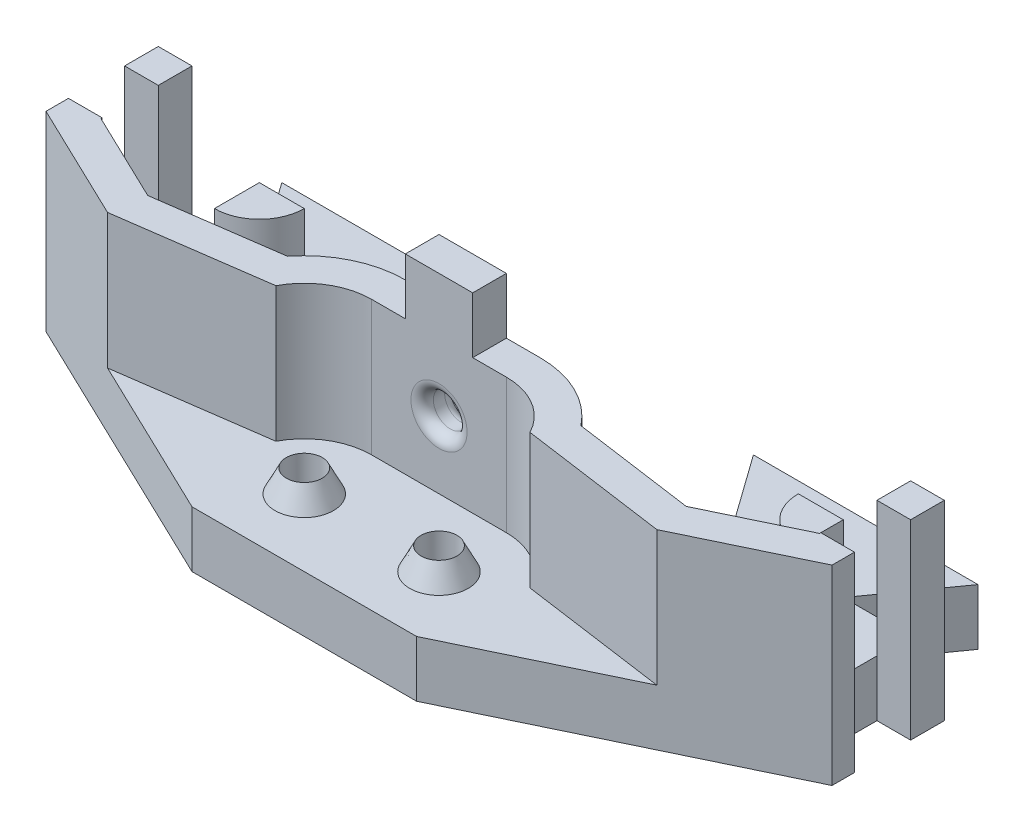
SolidWorks part; units mm, degrees
ref_plane "Front Plane" through (0, 0, 0) normal (0, 0, 1) x (1, 0, 0)
ref_plane "Top Plane" through (0, 0, 0) normal (0, 1, 0) x (1, 0, 0)
ref_plane "Right Plane" through (0, 0, 0) normal (1, 0, 0) x (0, 0, -1)
sketch "Sketch1" plane through (0, 0, 0) normal (0, 1, 0) x (1, 0, 0)
  line L0 (0, 0) -> (20, 0)
  line L1 (10, 0) -> (10, 12) construction
  line L2 (10, 12) -> (-25, 12) construction
  line L3 (0, 0) -> (-25, 12)
  line L4 (-25, 12) -> (-25, 22)
  line L5 (-25, 22) -> (45, 22)
  line L6 (45, 22) -> (45, 12)
  line L7 (45, 12) -> (20, 0)
  dimension "D1" = 35
  dimension "D2" = 20
  dimension "D3" = 12
  dimension "D4" = 70
  dimension "D5" = 10
  dimension "D6" = 10
extrude "Boss-Extrude1" add sketch "Sketch1" along normal blind 5
sketch "Sketch2" plane through (0, 5, 0) normal (0, 1, 0) x (1, 0, 0)
  line L0 (10, 0) -> (10, 22) construction
  line L1 (0, 0) -> (20, 0) construction
  line L2 (45, 22) -> (-25, 22) construction
  circle A0 centre (4, 6) radius 1.6
  circle A1 centre (16, 6) radius 1.6
  dimension "D1" = 3.2
  dimension "D2" = 6
  dimension "D3" = 6
extrude "Cut-Extrude1" cut sketch "Sketch2" against normal blind 3
sketch "Sketch3" plane through (0, 5, 0) normal (0, 1, 0) x (1, 0, 0)
  line L0 (4, 6) -> (-8.7631, 4.2063) construction
  line L1 (-25, 12) -> (0, 0) construction
  line L2 (-8.7631, 4.2063) -> (-8.7631, 22) construction
  line L3 (45, 22) -> (-25, 22) construction
  line L4 (-2.3815, 5.1031) -> (-2.8686, 8.5691) construction
  line L5 (-2.8686, 8.5691) -> (4.0027, 9.5348) construction
  line L6 (-1.3131, 8.7877) -> (-14.4587, 6.9402)
  line L7 (10, 0) -> (10, 22) construction
  line L8 (0, 0) -> (20, 0) construction
  line L10 (-14.4587, 6.9402) -> (-25, 12)
  line L11 (-25, 12) -> (-25, 22)
  line L12 (-25, 22) -> (-22, 22)
  line L13 (-21.9703, 13.8734) -> (-25, 15.3277) construction
  line L14 (-21.9703, 13.8734) -> (-9.0961, 7.6939) construction
  line L15 (-19.7294, 9.4701) -> (-13.715, 22) construction
  line L17 (-3.069, 11.5704) -> (-13.9782, 10.0372)
  line L19 (-7.8859, 7.8639) -> (-9.8726, 22) construction
  line L21 (4, 12) -> (4, 15) construction
  line L30 (-22, 22) -> (-22, 13.8877)
  line L32 (0.4296, 9.0326) -> (0.012, 12.0034) construction
  line L33 (0.012, 12.0034) -> (-19.3407, 9.2836) construction
  line L34 (-22, 13.8877) -> (-13.9782, 10.0372)
  line L35 (4, 15) -> (16, 15)
  line L36 (4, 12) -> (16, 12)
  line L37 (21.3131, 8.7877) -> (34.4587, 6.9402)
  line L38 (34.4587, 6.9402) -> (45, 12)
  line L39 (45, 12) -> (45, 22)
  line L40 (45, 22) -> (42, 22)
  line L41 (42, 22) -> (42, 13.8877)
  line L42 (42, 13.8877) -> (33.9782, 10.0372)
  line L43 (23.069, 11.5704) -> (33.9782, 10.0372)
  arc A0 (-1.3131, 8.7877) -> (4, 12) centre (4, 6) cw
  arc A4 (4, 15) -> (-3.069, 11.5704) centre (4, 6) ccw
  arc A5 (21.3131, 8.7877) -> (16, 12) centre (16, 6) ccw
  arc A6 (16, 15) -> (23.069, 11.5704) centre (16, 6) cw
  point P34 (10, 12)
  point P35 (10, 12)
  point P36 (10, 15)
  point P52 (10, 15)
  dimension "D4" = 6
  dimension "D1" = 82
  dimension "D2" = 3.5
  dimension "D3" = 90
  dimension "D5" = 90
  dimension "D6" = 90
  dimension "D7" = 3
  dimension "D8" = 3
  dimension "D9" = 3
  dimension "D10" = 3
  dimension "D11" = 3
  dimension "D12" = 90
extrude "Boss-Extrude2" add sketch "Sketch3" along normal blind 12
ref_plane "Plane1" through (0, 0, -6) normal (0, 0, 1) x (1, 0, 0)
sketch "Sketch6" plane through (0, 0, -6) normal (0, 0, 1) x (1, 0, 0)
  line L0 (2.4, 5) -> (2.4, 7)
  line L1 (2.4, 7) -> (1.4, 5)
  line L2 (1.4, 5) -> (2.4, 5)
  line L3 (2.4, 5) -> (5.6, 5) construction
  line L4 (4, 5) -> (4, 7.7373) construction
  dimension "D1" = 2
  dimension "D2" = 1
revolve "Revolve1" add sketch "Sketch6" angle 360 about L4
sketch "Sketch7" plane through (0, 0, -6) normal (0, 0, 1) x (1, 0, 0)
  line L0 (14.4, 5) -> (14.4, 7)
  line L1 (14.4, 7) -> (13.4, 5)
  line L2 (13.4, 5) -> (14.4, 5)
  line L3 (14.4, 5) -> (17.6, 5) construction
  line L4 (16, 5) -> (16, 8.947) construction
  dimension "D1" = 2
  dimension "D2" = 1
revolve "Revolve2" add sketch "Sketch7" angle 360 about L4
sketch "Sketch8" plane through (0, 0, -12) normal (0, 0, 1) x (1, 0, 0)
  line L0 (10, 17) -> (10, 5) construction
  line L1 (4, 17) -> (16, 17) construction
  line L2 (4, 5) -> (16, 5) construction
  circle A0 centre (10, 11) radius 1.5
  dimension "D1" = 3
extrude "Cut-Extrude2" cut sketch "Sketch8" against normal blind 3
fillet "Fillet1" radius 1 2 edges at (11.5, 11, -15) (11.5, 11, -12)
sketch "Sketch9" plane through (0, 17, 0) normal (0, 1, 0) x (1, 0, 0)
  line L0 (10, 12) -> (10, 15) construction
  line L1 (4, 12) -> (16, 12) construction
  line L2 (16, 15) -> (4, 15) construction
  line L3 (16, 15) -> (4, 15) construction
  line L4 (7, 12) -> (13, 12)
  line L5 (7, 12) -> (7, 15)
  line L6 (7, 15) -> (13, 15)
  line L7 (13, 12) -> (13, 15)
  dimension "D1" = 3
  dimension "D2" = 3
extrude "Boss-Extrude3" add sketch "Sketch9" along normal blind 5
sketch "Sketch12" plane through (0, 17, 0) normal (0, 1, 0) x (1, 0, 0)
  line L0 (-25, 22) -> (-25, 12) construction
  line L1 (-25, 19) -> (-22, 19)
  line L2 (-25, 19) -> (-25, 14)
  line L3 (-25, 14) -> (-22, 14)
  line L4 (-22, 19) -> (-22, 14)
  line L5 (-22, 13.8877) -> (-22, 22) construction
  line L6 (-22, 22) -> (-25, 22) construction
  line L7 (10, 22) -> (10, 0) construction
  line L8 (42, 22) -> (-22, 22) construction
  line L9 (0, 0) -> (20, 0) construction
  line L10 (45, 14) -> (42, 14)
  line L11 (42, 19) -> (42, 14)
  line L12 (45, 19) -> (42, 19)
  line L13 (45, 19) -> (45, 14)
  dimension "D1" = 3
  dimension "D2" = 5
extrude "Cut-Extrude4" cut sketch "Sketch12" against normal blind 17
sketch "Sketch14" plane through (0, 5, 0) normal (0, 1, 0) x (1, 0, 0)
  line L0 (42, 22) -> (-22, 22) construction
  line L1 (32, 22) -> (36, 22)
  line L2 (32, 22) -> (32, 18)
  line L3 (32, 18) -> (36, 18)
  line L4 (36, 22) -> (36, 18)
  line L5 (10, 22) -> (10, 0) construction
  line L6 (0, 0) -> (20, 0) construction
  line L7 (-12, 18) -> (-16, 18)
  line L8 (-16, 22) -> (-16, 18)
  line L9 (-12, 22) -> (-16, 22)
  line L10 (-12, 22) -> (-12, 18)
  dimension "D1" = 10
  dimension "D2" = 4
  dimension "D3" = 4
extrude "Boss-Extrude5" add sketch "Sketch14" along normal blind 6
fillet "Fillet3" radius 4 1 edges at (32, 8, -18) type face fillet first side face at (34, 8, -18) second side face at (32, 8, -20)
fillet "Fillet4" radius 4 1 edges at (-12, 8, -18) type face fillet first side face at (-12, 8, -20) second side face at (-14, 8, -18)
sketch "Sketch15" plane through (0, 5, 0) normal (0, 1, 0) x (1, 0, 0)
  line L0 (-16, 22) -> (-21, 29)
  line L1 (-16, 22) -> (-22, 22) construction
  line L2 (-21, 29) -> (-1, 29)
  line L3 (-1, 29) -> (-6, 22)
  line L4 (32, 22) -> (-12, 22) construction
  line L5 (-16, 22) -> (-6, 22)
  line L6 (10, 22) -> (10, 29) construction
  line L7 (36, 22) -> (26, 22)
  line L8 (21, 29) -> (26, 22)
  line L9 (41, 29) -> (21, 29)
  line L10 (36, 22) -> (41, 29)
  dimension "D1" = 4
  dimension "D2" = 5
  dimension "D3" = 10
  dimension "D4" = 5
  dimension "D5" = 7
extrude "Boss-Extrude6" add sketch "Sketch15" against normal blind 5
